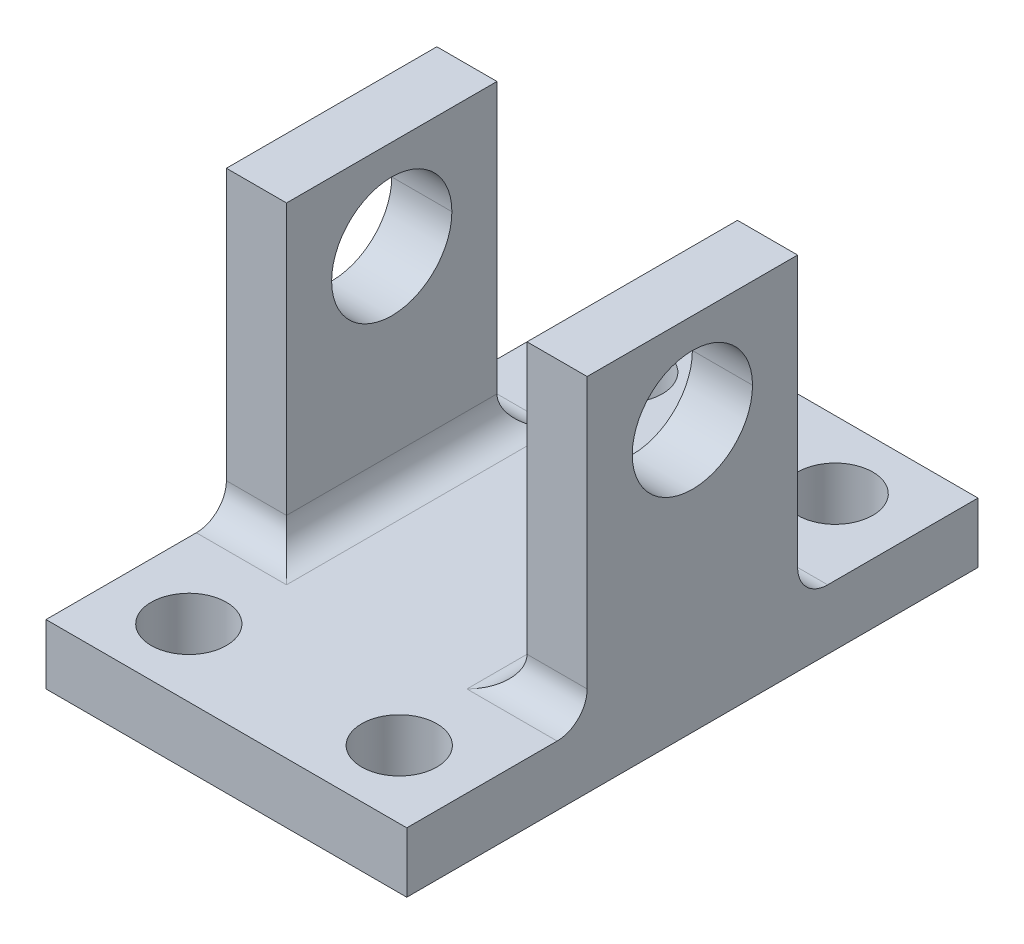
SolidWorks part; units mm, degrees
ref_plane "Front Plane" through (0, 0, 0) normal (0, 0, 1) x (1, 0, 0)
ref_plane "Top Plane" through (0, 0, 0) normal (0, 1, 0) x (1, 0, 0)
ref_plane "Right Plane" through (0, 0, 0) normal (1, 0, 0) x (0, 0, -1)
sketch "Sketch1" plane through (0, 0, 0) normal (0, 0, 1) x (1, 0, 0)
  line L0 (0, 0) -> (0, 24) construction
  line L1 (0, 24) -> (-4, 24)
  line L2 (-4, 24) -> (-4, 4)
  line L3 (-4, 4) -> (-20, 4)
  line L5 (-24, 0) -> (0, 0)
  line L6 (-24, 0) -> (-24, 24) construction
  line L7 (-24, 24) -> (-20, 24)
  line L8 (-20, 24) -> (-20, 4)
  line L12 (-24, 0) -> (-24, 24)
  line L16 (0, 0) -> (0, 24)
  point P5 (-32, 0.1027)
  point P8 (0, 0.1957)
  dimension "D1" = 4
  dimension "D2" = 4
  dimension "D3" = 24
  dimension "D4" = 16
  dimension "D5" = 4
extrude "Boss-Extrude1" add sketch "Sketch1" along normal mid plane 38 contours L5 L16 L1 L2 L3 L8 L7 L12
sketch "Sketch2" plane through (-4, 0, 0) normal (-1, 0, 0) x (0, 0, 1)
  circle A0 centre (0, 18) radius 4
  point P2 (0, 0)
  dimension "D1" = 8
  dimension "D2" = 18
extrude "M8 hole" cut sketch "Sketch2" against normal through all both and the other way through all
sketch "Sketch3" plane through (0, 4, 0) normal (0, 1, 0) x (1, 0, 0)
  line L0 (0, 0) -> (-24, 0) construction
  line L1 (-24, -19) -> (-24, 19) construction
  line L2 (-12, 19) -> (-12, -19) construction
  line L3 (-4, 19) -> (-20, 19) construction
  line L4 (-4, -19) -> (-20, -19) construction
  circle A0 centre (-19, 14.5) radius 2.5
  circle A1 centre (-5, 14.5) radius 2.5
  circle A2 centre (-5, -14.5) radius 2.5
  circle A3 centre (-19, -14.5) radius 2.5
  point P11 (-32, 0)
  dimension "D1" = 5
  dimension "D2" = 14.5
  dimension "D3" = 7
fillet "Fillet2" [suppressed] radius 5
extrude "M5 holes" cut sketch "Sketch3" against normal through all both and the other way through all
sketch "Sketch4" plane through (-24, 0, 0) normal (-1, 0, 0) x (0, 0, 1)
  line L0 (0, 0) -> (0, 24) construction
  line L1 (-19, 24) -> (-7, 24)
  line L2 (-19, 24) -> (-19, 4)
  line L3 (-19, 4) -> (-7, 4)
  line L4 (-7, 24) -> (-7, 4)
  line L9 (19, 0) -> (-19, 0) construction
  line L10 (19, 24) -> (-19, 24) construction
  line L11 (19, 4) -> (7, 4)
  line L12 (19, 24) -> (19, 4)
  line L13 (19, 24) -> (7, 24)
  line L14 (7, 24) -> (7, 4)
  dimension "D1" = 12
  dimension "D2" = 4
extrude "trim down sides" cut sketch "Sketch4" against normal through all
fillet "Fillet3" radius 2 6 edges at (-22, 4, -7) (-2, 4, -7) (-4, 4, 0) (-2, 4, 7) (-20, 4, 0) (-22, 4, 7)
ref_axis "Axis1" through (0, 18, 0) along (-1, 0, 0)
ref_plane "Plane1" through (0, 18, 0) normal (0, 1, 0) x (1, 0, 0)
split line "splitlineforFEA"
sketch "Sketch5" plane through (0, 4, 0) normal (0, 1, 0) x (1, 0, 0)
  circle A0 centre (-19, 14.5) radius 4.25
  dimension "D1" = 8.5
